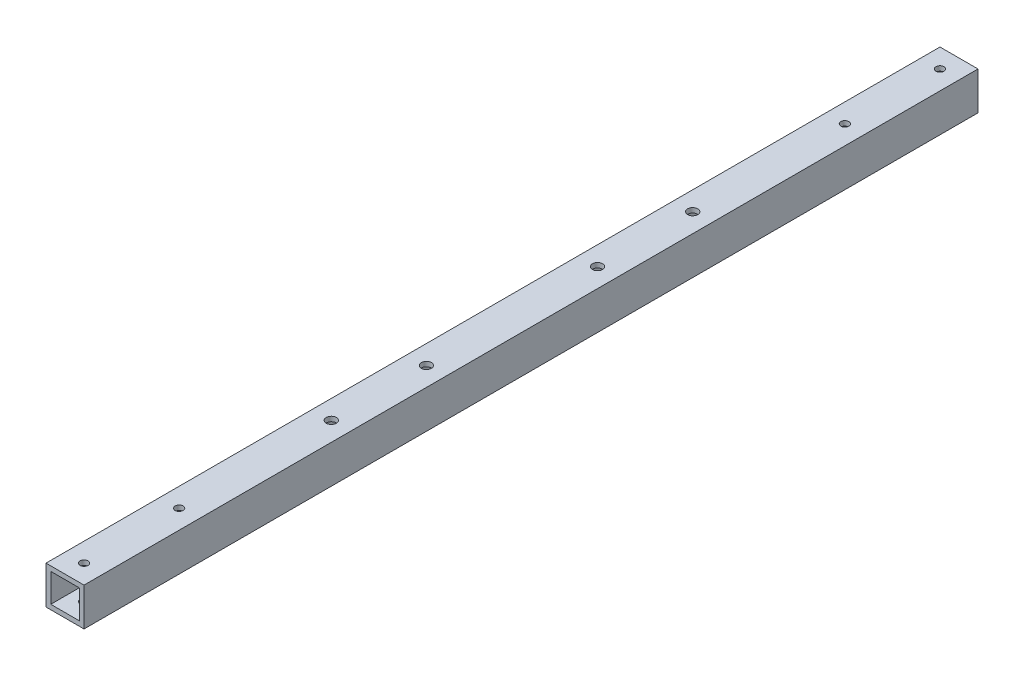
SolidWorks part; units mm, degrees
ref_plane "Front Plane" through (0, 0, 0) normal (0, 0, 1) x (1, 0, 0)
ref_plane "Top Plane" through (0, 0, 0) normal (0, 1, 0) x (1, 0, 0)
ref_plane "Right Plane" through (0, 0, 0) normal (1, 0, 0) x (0, 0, -1)
sketch "Sketch1" plane through (0, 0, 0) normal (0, 0, 1) x (1, 0, 0)
  line L0 (3.175, 22.225) -> (22.225, 22.225)
  line L1 (0, 0) -> (25.4, 0)
  line L2 (0, 0) -> (0, 25.4)
  line L3 (0, 25.4) -> (25.4, 25.4)
  line L4 (25.4, 0) -> (25.4, 25.4)
  line L5 (22.225, 3.175) -> (22.225, 22.225)
  line L6 (3.175, 3.175) -> (22.225, 3.175)
  line L7 (3.175, 3.175) -> (3.175, 22.225)
  dimension "D1" = 25.4
  dimension "D2" = 25.4
  dimension "D3" = 3.175
extrude "Boss-Extrude1" add sketch "Sketch1" along normal blind 596.9
sketch "Sketch2" plane through (0, 25.4, 0) normal (0, 1, 0) x (1, 0, 0)
  line L0 (25.4, -596.9) -> (25.4, 0) construction
  line L1 (25.4, -596.9) -> (0, -596.9) construction
  line L2 (0, -298.45) -> (25.4, -298.45) construction
  line L3 (0, -596.9) -> (0, 0) construction
  circle A0 centre (12.7, -584.2) radius 2.667
  circle A1 centre (12.7, -12.7) radius 2.667
  circle A2 centre (12.7, -520.7) radius 2.667
  circle A3 centre (12.7, -76.2) radius 2.667
  dimension "D1" = 5.334
  dimension "D4" = 5.334
  dimension "D2" = 12.7
  dimension "D3" = 12.7
  dimension "D5" = 12.7
  dimension "D6" = 63.5
extrude "Cut-Extrude1" cut sketch "Sketch2" against normal through all
sketch "Sketch4" plane through (0, 25.4, 0) normal (0, 1, 0) x (1, 0, 0)
  line L0 (0, -298.45) -> (25.4, -298.45) construction
  line L1 (0, -596.9) -> (0, 0) construction
  line L2 (25.4, -596.9) -> (25.4, 0) construction
  circle A0 centre (12.7, -419.1) radius 3.3782
  circle A1 centre (12.7, -355.6) radius 3.3782
  circle A2 centre (12.7, -520.7) radius 2.667 construction
  circle A4 centre (12.7, -177.8) radius 3.3782
  circle A5 centre (12.7, -241.3) radius 3.3782
  dimension "D1" = 101.6
  dimension "D2" = 63.5
  dimension "D5" = 6.7564
  dimension "D6" = 6.7564
  dimension "D3" = 12.7
  dimension "D4" = 12.7
extrude "Cut-Extrude3" cut sketch "Sketch4" against normal blind 25.4
